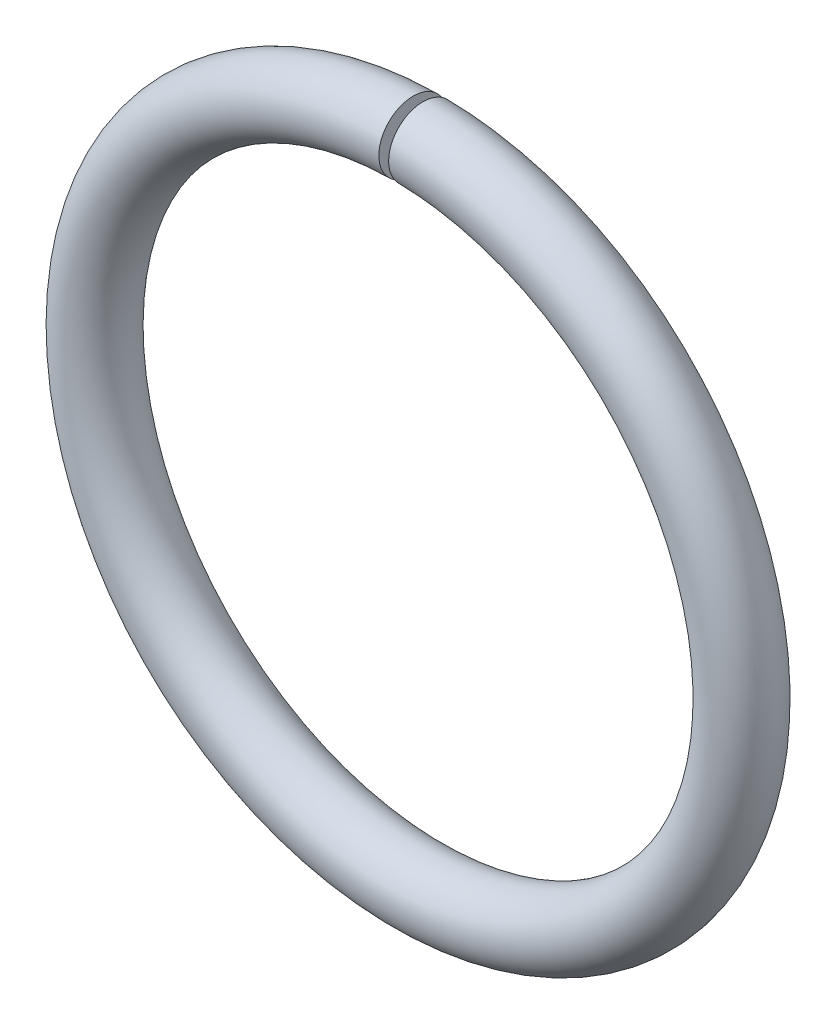
SolidWorks part; units mm, degrees
ref_plane "Спереди" through (0, 0, 0) normal (0, 0, 1) x (1, 0, 0)
ref_plane "Сверху" through (0, 0, 0) normal (0, 1, 0) x (1, 0, 0)
ref_plane "Справа" through (0, 0, 0) normal (1, 0, 0) x (0, 0, -1)
sketch "Эскиз1" plane through (0, 0, 0) normal (1, 0, 0) x (0, 0, -1)
  line L0 (0, 0) -> (0, 6.6) construction
  line L1 (0, 0) -> (7.5648, 0) construction
  circle A0 centre (0, 6.6) radius 0.7
  dimension "D1" = 1.4
  dimension "D2" = 13.2
revolve "Повернуть1" add sketch "Эскиз1" angle 360 about L1
sketch "Эскиз2" plane through (0, 0, 0) normal (0, 0, 1) x (1, 0, 0)
  line L0 (0, 10.464) -> (0, 4.656) construction
  line L2 (-0.1, 7.6578) -> (0.1, 7.6578)
  line L3 (-0.1, 7.6578) -> (-0.1, 5.0403)
  line L4 (-0.1, 5.0403) -> (0.1, 5.0403)
  line L5 (0.1, 7.6578) -> (0.1, 5.0403)
  dimension "D1" = 0.1
  dimension "D2" = 0.2
extrude "Вытянуть1" cut sketch "Эскиз2" against normal through all and the other way through all
ref_axis "Ось1" through (0, 0, 0) along (0, 0, 1)
